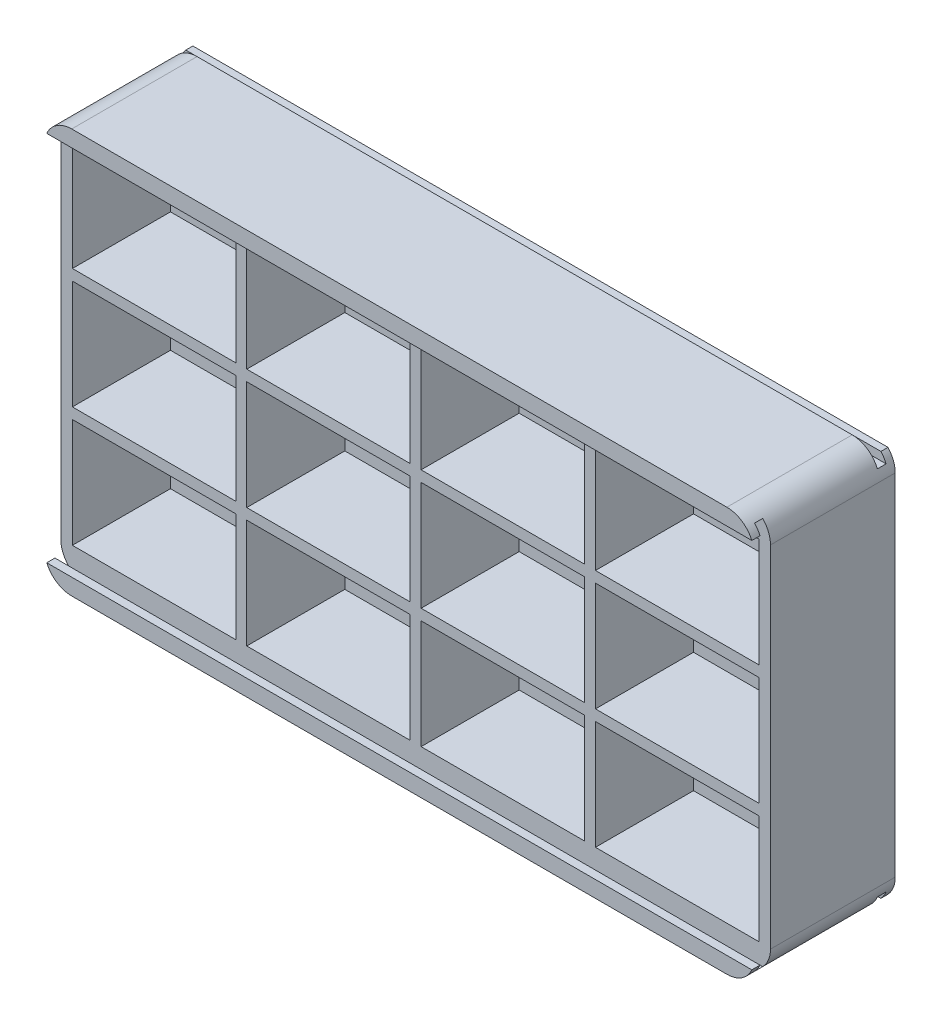
SolidWorks part; units mm, degrees
ref_plane "Alzado" through (0, 0, 0) normal (0, 0, 1) x (1, 0, 0)
ref_plane "Planta" through (0, 0, 0) normal (0, 1, 0) x (1, 0, 0)
ref_plane "Vista lateral" through (0, 0, 0) normal (1, 0, 0) x (0, 0, -1)
sketch "Croquis1" plane through (0, 0, 0) normal (0, 0, 1) x (1, 0, 0)
  line L0 (32, 0) -> (32, -20)
  line L1 (0, 0) -> (30, 0)
  line L2 (0, 0) -> (0, -20)
  line L3 (0, -20) -> (30, -20)
  line L4 (30, 0) -> (30, -20)
  line L5 (32, 0) -> (62, 0)
  line L6 (62, 0) -> (62, -20)
  line L7 (32, -20) -> (62, -20)
  line L8 (64, 0) -> (64, -20)
  line L9 (64, 0) -> (94, 0)
  line L10 (94, 0) -> (94, -20)
  line L11 (64, -20) -> (94, -20)
  line L12 (96, 0) -> (96, -20)
  line L13 (96, 0) -> (126, 0)
  line L14 (126, 0) -> (126, -20)
  line L15 (96, -20) -> (126, -20)
  line L16 (32, -22) -> (32, -42)
  line L17 (32, -22) -> (62, -22)
  line L18 (62, -22) -> (62, -42)
  line L19 (32, -42) -> (62, -42)
  line L20 (64, -22) -> (64, -42)
  line L21 (64, -22) -> (94, -22)
  line L22 (94, -22) -> (94, -42)
  line L23 (64, -42) -> (94, -42)
  line L24 (96, -22) -> (96, -42)
  line L25 (96, -22) -> (126, -22)
  line L26 (126, -22) -> (126, -42)
  line L27 (96, -42) -> (126, -42)
  line L28 (32, -44) -> (32, -64)
  line L29 (32, -44) -> (62, -44)
  line L30 (62, -44) -> (62, -64)
  line L31 (32, -64) -> (62, -64)
  line L32 (64, -44) -> (64, -64)
  line L33 (64, -44) -> (94, -44)
  line L34 (94, -44) -> (94, -64)
  line L35 (64, -64) -> (94, -64)
  line L36 (96, -44) -> (96, -64)
  line L37 (96, -44) -> (126, -44)
  line L38 (126, -44) -> (126, -64)
  line L39 (96, -64) -> (126, -64)
  line L40 (0, -22) -> (0, -42)
  line L41 (0, -22) -> (30, -22)
  line L42 (30, -22) -> (30, -42)
  line L43 (0, -42) -> (30, -42)
  line L44 (0, -44) -> (0, -64)
  line L45 (0, -44) -> (30, -44)
  line L46 (30, -44) -> (30, -64)
  line L47 (0, -64) -> (30, -64)
  line L48 (126, -64) -> (128.1213, -66.1213) construction
  line L49 (0, 0) -> (-2.1213, 2.1213) construction
  line L51 (128.1213, -66.1213) -> (-2.1213, -66.1213)
  line L52 (128.1213, -66.1213) -> (128.1213, 2.1213)
  line L53 (128.1213, 2.1213) -> (-2.1213, 2.1213)
  line L54 (-2.1213, -66.1213) -> (-2.1213, 2.1213)
  dimension "D1" = 30
  dimension "D2" = 20
  dimension "D5" = 3
  dimension "D6" = 3
  dimension "D3" = 4
  dimension "D4" = 3
extrude "Celdas" add sketch "Croquis1" along normal blind 20
sketch "Croquis2" plane through (128.1213, 0, 0) normal (1, 0, 0) x (0, 0, -1)
  line L0 (-20, 2.1213) -> (0, 2.1213) construction
  line L1 (0, -66.1213) -> (-2, -66.1213)
  line L2 (0, -66.1213) -> (0, 2.1213)
  line L3 (0, 2.1213) -> (-2, 2.1213)
  line L4 (-2, -66.1213) -> (-2, 2.1213)
  dimension "D1" = 2
extrude "Base" add sketch "Croquis2" against normal through all
sketch "Croquis3" plane through (0, 0, 20) normal (0, 0, 1) x (1, 0, 0)
  line L1 (-2.1213, -66.1213) -> (128.1213, -66.1213)
  line L2 (-2.1213, -66.1213) -> (-2.1213, -69.1213)
  line L3 (-2.1213, -69.1213) -> (128.1213, -69.1213)
  line L4 (128.1213, -66.1213) -> (128.1213, -69.1213)
  line L5 (-2.1213, 2.1213) -> (128.1213, 2.1213)
  line L6 (-2.1213, 2.1213) -> (-2.1213, 5.1213)
  line L7 (-2.1213, 5.1213) -> (128.1213, 5.1213)
  line L8 (128.1213, 2.1213) -> (128.1213, 5.1213)
  dimension "D1" = 3
  dimension "D2" = 3
extrude "Excedente" add sketch "Croquis3" against normal blind 20 and the other way blind 3 contours L6 L5 L8 L7 | L2 L1 L4 L3
sketch "Croquis4" plane through (-2.1213, 0, 0) normal (-1, 0, 0) x (0, 0, 1)
  line L0 (23, 3.6213) -> (20, 3.6213) construction
  line L1 (23, 2.1213) -> (23, 5.1213) construction
  line L5 (23, -66.1213) -> (23, -69.1213) construction
  line L6 (20, 2.1213) -> (21.5, 2.1213) construction
  line L7 (23, 2.1213) -> (20, 2.1213) construction
  line L8 (21.5, 2.1213) -> (21.5, 3.6213) construction
  line L9 (21.5, 3.6213) -> (21.5, -67.6213) construction
  line L15 (20, -67.6213) -> (23, -67.6213) construction
  line L20 (21.5, -67.6213) -> (20, -67.6213)
  line L21 (21.5, -67.6213) -> (21.5, 3.6213)
  line L22 (21.5, 3.6213) -> (20, 3.6213)
  line L23 (20, -67.6213) -> (20, 3.6213)
extrude "Ranura" cut sketch "Croquis4" against normal through all
sketch "Croquis6" plane through (-2.1213, 0, 0) normal (-1, 0, 0) x (0, 0, 1)
  line L2 (0, 2.1213) -> (0, -66.1213)
  line L3 (0, 5.1213) -> (0, -69.1213) construction
  line L4 (23, 5.1213) -> (0, 5.1213) construction
  line L5 (0, -66.1213) -> (-1.5, -66.1213)
  line L8 (-1.5, -67.6213) -> (-3, -67.6213)
  line L9 (-3, 3.6213) -> (-3, -67.6213)
  line L10 (-1.5, -66.1213) -> (-1.5, -67.6213)
  line L11 (-3, 3.6213) -> (-1.5, 3.6213)
  line L12 (-1.5, 3.6213) -> (-1.5, 2.1213)
  line L13 (-1.5, 2.1213) -> (0, 2.1213)
  line L15 (23, -69.1213) -> (0, -69.1213) construction
  dimension "D1" = 1.5
  dimension "D2" = 1.5
  dimension "D3" = 1.5
  dimension "D4" = 1.5
extrude "Pestaña" add sketch "Croquis6" against normal through all
sketch "Croquis7" plane through (-2.1213, 0, 0) normal (-1, 0, 0) x (0, 0, 1)
  line L1 (-0.1, 2.0213) -> (-1.6, 2.0213)
  line L2 (-1.6, 2.0213) -> (-1.6, 3.5213)
  line L3 (-1.6, 3.5213) -> (-2.9, 3.5213)
  line L4 (-2.9, 3.5213) -> (-2.9, -67.5213)
  line L5 (-2.9, -67.5213) -> (-1.6, -67.5213)
  line L6 (-1.6, -67.5213) -> (-1.6, -66.0213)
  line L7 (-1.6, -66.0213) -> (-0.1, -66.0213)
  line L8 (-0.1, 2.0213) -> (0, 2.0213)
  line L9 (-0.1, -66.0213) -> (0, -66.0213)
  line L10 (0, 2.0213) -> (0, 2.1213)
  line L11 (0, -66.1213) -> (0, 2.1213) construction
  line L20 (0, 2.1213) -> (-1.5, 2.1213)
  line L21 (-1.5, 2.1213) -> (-1.5, 3.6213)
  line L22 (-1.5, 3.6213) -> (-3, 3.6213)
  line L23 (-3, 3.6213) -> (-3, -67.6213)
  line L24 (-3, -67.6213) -> (-1.5, -67.6213)
  line L25 (-1.5, -67.6213) -> (-1.5, -66.1213)
  line L26 (-1.5, -66.1213) -> (0, -66.1213)
  line L27 (0, -66.1213) -> (0, -66.0213)
  line L28 (-0.1, -66.0213) -> (-0.1, 2.0213) construction
  dimension "D1" = 0.1
extrude "3D-Fix" cut sketch "Croquis7" against normal through all
fillet "Redondeo" radius 5 4 edges at (128.1213, 5.1213, 11.5) (128.1213, -69.1213, 11.5) (-2.1213, -69.1213, 11.5) (-2.1213, 5.1213, 11.5)
